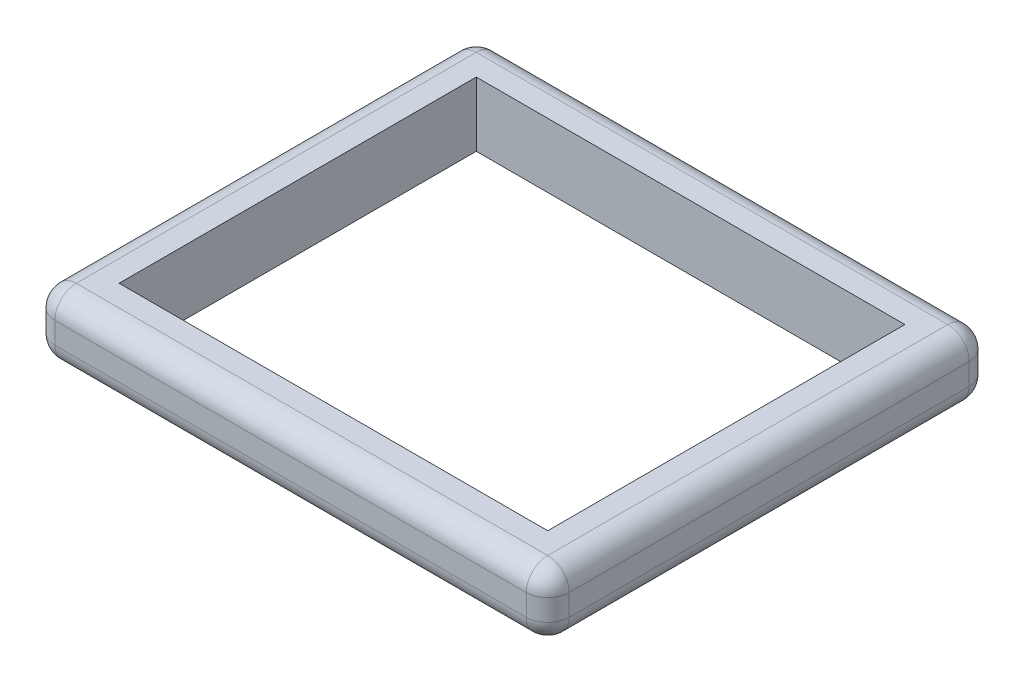
SolidWorks part; units mm, degrees
ref_plane "Front Plane" through (0, 0, 0) normal (0, 0, 1) x (1, 0, 0)
ref_plane "Top Plane" through (0, 0, 0) normal (0, 1, 0) x (1, 0, 0)
ref_plane "Right Plane" through (0, 0, 0) normal (1, 0, 0) x (0, 0, -1)
sketch "Sketch1" plane through (0, 0, 0) normal (0, 1, 0) x (1, 0, 0)
  line L5 (-381, 317.5) -> (381, 317.5)
  line L6 (-381, 317.5) -> (-381, -317.5)
  line L11 (-381, -317.5) -> (381, -317.5)
  line L12 (381, 317.5) -> (381, -317.5)
  line L13 (-381, 317.5) -> (381, -317.5) construction
  line L14 (-381, -317.5) -> (381, 317.5) construction
  line L15 (-457.2, 393.7) -> (457.2, 393.7)
  line L16 (-457.2, 393.7) -> (-457.2, -393.7)
  line L17 (-457.2, -393.7) -> (457.2, -393.7)
  line L18 (457.2, 393.7) -> (457.2, -393.7)
  line L19 (-457.2, 393.7) -> (457.2, -393.7) construction
  line L20 (-457.2, -393.7) -> (457.2, 393.7) construction
  point P0 (0, 0)
  point P1 (0, 0)
  point P5 (0, 0)
  point P8 (0, 0)
  dimension "D1" = 635
  dimension "D2" = 762
  dimension "D3" = 787.4
  dimension "D4" = 914.4
extrude "Boss-Extrude1" add sketch "Sketch1" along normal blind 114.3
sketch "Sketch3" plane through (0, 0, 317.5) normal (0, 0, -1) x (-1, 0, 0)
  line L0 (-36.0135, 74.4613) -> (65.6865, 74.4613)
  line L1 (241.3, 74.4613) -> (-241.3, 74.4613) construction
fillet "Fillet2" radius 38.1 4 edges at (457.2, 57.15, 393.7) (-457.2, 57.15, 393.7) (-457.2, 57.15, -393.7) (457.2, 57.15, -393.7)
fillet "Fillet3" radius 38.1 8 edges at (446.0408, 114.3, 382.5408) (0, 114.3, 393.7) (-446.0408, 114.3, 382.5408) (-457.2, 114.3, 0) (-446.0408, 114.3, -382.5408) (0, 114.3, -393.7) (446.0408, 114.3, -382.5408) (457.2, 114.3, 0)
fillet "Fillet4" radius 38.1 8 edges at (446.0408, 0, 382.5408) (0, 0, 393.7) (-446.0408, 0, 382.5408) (-457.2, 0, 0) (-446.0408, 0, -382.5408) (0, 0, -393.7) (446.0408, 0, -382.5408) (457.2, 0, 0)
sketch "Sketch4" plane through (0, 0, -317.5) normal (0, 0, 1) x (1, 0, 0)
  line L0 (-52.6776, 114.3835) -> (-16.7869, 114.3835) construction
  line L1 (273.05, 114.3835) -> (-273.05, 114.3835) construction
